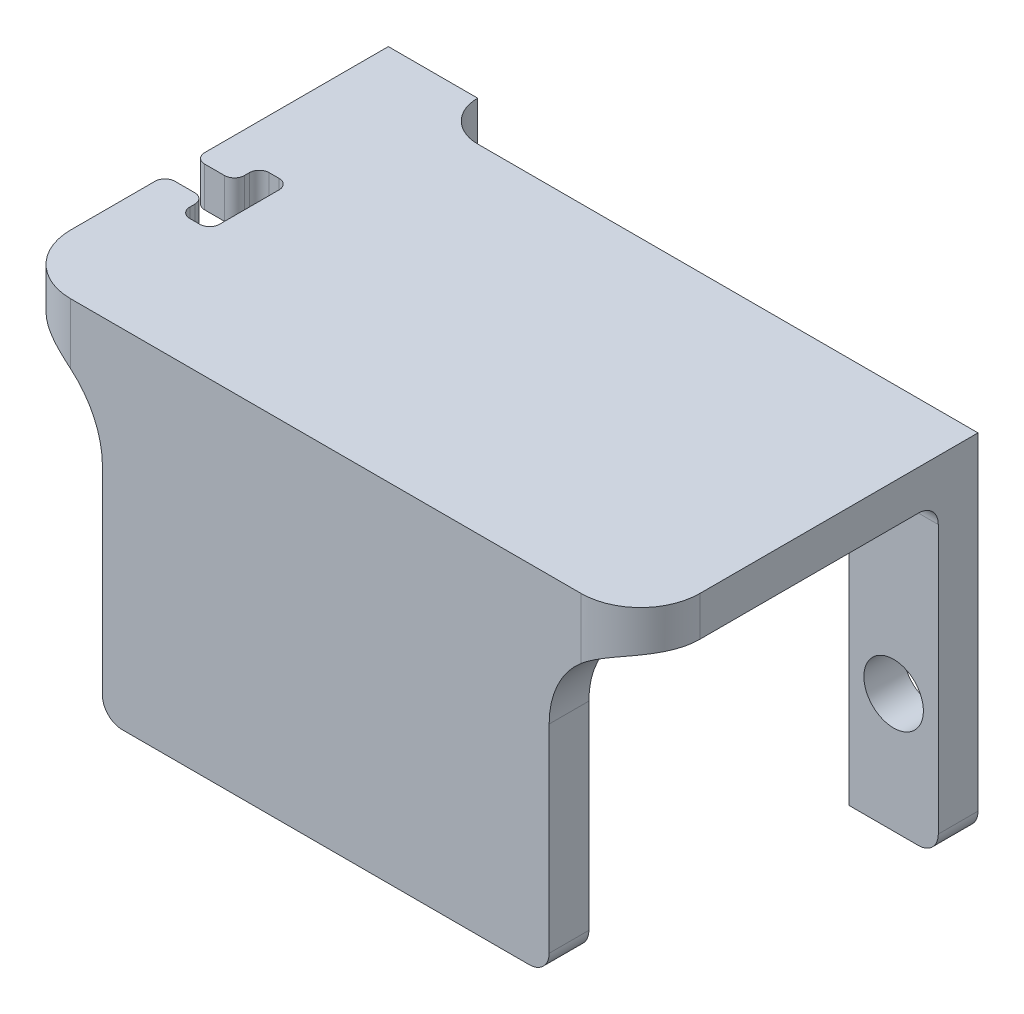
SolidWorks part; units mm, degrees
ref_plane "前视基准面" through (0, 0, 0) normal (0, 0, 1) x (1, 0, 0)
ref_plane "上视基准面" through (0, 0, 0) normal (0, 1, 0) x (1, 0, 0)
ref_plane "右视基准面" through (0, 0, 0) normal (1, 0, 0) x (0, 0, -1)
other "Configuration Table"
sketch "草图1" plane through (0, 0, 0) normal (0, 0, 1) x (1, 0, 0)
  line L0 (0, 2.6955) -> (0, -2.6955) construction
  line L1 (15.85, -6) -> (11.35, -6)
  line L2 (-15.85, 6) -> (-11.35, 6)
  line L3 (-15.85, 6) -> (-15.85, -6)
  line L4 (-15.85, -6) -> (-11.35, -6)
  line L5 (-11.35, 6) -> (-11.35, -6)
  line L6 (11.35, 6) -> (11.35, -6)
  line L7 (15.85, 6) -> (11.35, 6)
  line L8 (15.85, 6) -> (15.85, -6)
  point P13 (-11.35, 0)
  dimension "D1" = 12
  dimension "D2" = 4.5
  dimension "D3" = 22.7
extrude "凸台-拉伸1" add sketch "草图1" along normal blind 2
sketch "草图2" plane through (0, 0, 0) normal (0, 0, 1) x (1, 0, 0)
  line L1 (-15.85, 6) -> (-11.35, 6)
  line L2 (-15.85, 6) -> (-15.85, -6)
  line L3 (-15.85, -6) -> (-11.35, -6)
  line L4 (-11.35, 6) -> (-11.35, -6)
  point P4 (0, 0)
  point P6 (-15.75, 6)
  point P7 (-11.25, -6)
  point P8 (0, 0)
  point P9 (-10.1781, -7.1006)
  point P13 (-11.8934, -5.5098)
extrude "凸台-拉伸4" add sketch "草图2" against normal blind 2
sketch "草图4" plane through (0, 0, 2) normal (0, 0, -1) x (-1, 0, 0)
  line L1 (0, 6) -> (0, -6) construction
  line L2 (11.35, 6) -> (15.85, 6) construction
  circle A0 centre (13.6, 0) radius 1.5
  circle A1 centre (-13.6, 0) radius 1.5
  point P2 (0, 0)
  point P5 (0, 0)
  point P11 (13.6, 6)
  dimension "D1" = 3
extrude "切除-拉伸1" cut sketch "草图4" along normal through all
sketch "草图5" plane through (0, 0, 2) normal (0, 0, 1) x (1, 0, 0)
  line L0 (15.85, 6) -> (11.35, 6) construction
  line L1 (-15.85, 11.5) -> (15.85, 11.5)
  line L2 (-15.85, 11.5) -> (-15.85, 6)
  line L3 (-15.85, 6) -> (15.85, 6)
  line L4 (15.85, 11.5) -> (15.85, 6)
  line L5 (-15.85, 6) -> (-15.85, -6) construction
  line L6 (15.85, -6) -> (15.85, 6) construction
  dimension "D1" = 5.5
extrude "凸台-拉伸5" add sketch "草图5" against normal blind 2
sketch "草图6" plane through (0, 0, 2) normal (0, 0, 1) x (1, 0, 0)
  line L0 (15.85, 11.5) -> (-15.85, 11.5) construction
  line L1 (-15.85, 11.5) -> (15.85, 11.5)
  line L2 (-15.85, 11.5) -> (-15.85, 9.5)
  line L3 (-15.85, 9.5) -> (15.85, 9.5)
  line L4 (15.85, 11.5) -> (15.85, 9.5)
  line L5 (-15.85, 11.5) -> (-15.85, -6) construction
  line L6 (15.85, -6) -> (15.85, 11.5) construction
  dimension "D1" = 2
extrude "凸台-拉伸6" add sketch "草图6" along normal blind 15
sketch "草图7" plane through (0, 9.5, 0) normal (0, -1, 0) x (1, 0, 0)
  line L1 (-11.25, 17) -> (11.25, 17)
  line L2 (-11.25, 17) -> (-11.25, 15)
  line L3 (-11.25, 15) -> (11.25, 15)
  line L4 (11.25, 17) -> (11.25, 15)
  line L7 (-15.85, 17) -> (15.85, 17) construction
  point P6 (0, 17)
  point P7 (0, 17)
  dimension "D1" = 2
  dimension "D2" = 22.5
extrude "凸台-拉伸7" add sketch "草图7" along normal up to surface (15.5 mm away) up to face at (-13.6, -6, 0)
fillet "圆角3" radius 1 4 edges at (11.25, -6, 16) (-11.25, -6, 16) (-15.85, -6, 0) (15.85, -6, 1)
fillet "圆角4" radius 4.5 2 edges at (11.25, 9.5, 16) (-11.25, 9.5, 16)
fillet "圆角5" radius 1 2 edges at (0, 9.5, 15) (0, 9.5, 2)
fillet "圆角6" radius 3 2 edges at (15.85, 10.5, 17) (-15.85, 10.5, 17)
sketch "草图8" plane through (0, 6, 0) normal (0, 1, 0) x (1, 0, 0)
  line L1 (-15.85, 2) -> (-11.35, 2)
  line L2 (-15.85, 2) -> (-15.85, 0)
  line L3 (-15.85, 0) -> (-11.35, 0)
  line L4 (-11.35, 2) -> (-11.35, 0)
  point P4 (0, 0)
extrude "凸台-拉伸8" add sketch "草图8" along normal up to surface (5.5 mm away) up to face at (0, 11.5, 10.5404)
fillet "圆角7" radius 2 1 edges at (-11.35, 8.75, 0)
sketch "草图9" plane through (0, 9.5, 0) normal (0, -1, 0) x (1, 0, 0)
  line L0 (-15.85, 14) -> (-15.85, 3) construction
  line L1 (-15.85, 9.25) -> (-13.85, 9.25)
  line L2 (-15.85, 9.25) -> (-15.85, 7.75)
  line L3 (-15.85, 7.75) -> (-13.85, 7.75)
  line L5 (-13.85, 7.75) -> (-13.85, 6.5)
  line L6 (-13.85, 10.5) -> (-12.35, 10.5)
  line L7 (-13.85, 10.5) -> (-13.85, 9.25)
  line L8 (-13.85, 6.5) -> (-12.35, 6.5)
  line L9 (-12.35, 10.5) -> (-12.35, 6.5)
  point P6 (-15.85, 8.5)
  point P7 (-15.85, 8.5)
  dimension "D1" = 1.5
  dimension "D2" = 2
  dimension "D3" = 1.5
  dimension "D4" = 4
extrude "切除-拉伸2" cut sketch "草图9" against normal through all
fillet "圆角8" radius 0.5 8 edges at (-15.85, 10.5, 7.75) (-15.85, 10.5, 9.25) (-12.35, 10.5, 6.5) (-13.85, 10.5, 6.5) (-13.85, 10.5, 7.75) (-12.35, 10.5, 10.5) (-13.85, 10.5, 10.5) (-13.85, 10.5, 9.25)
